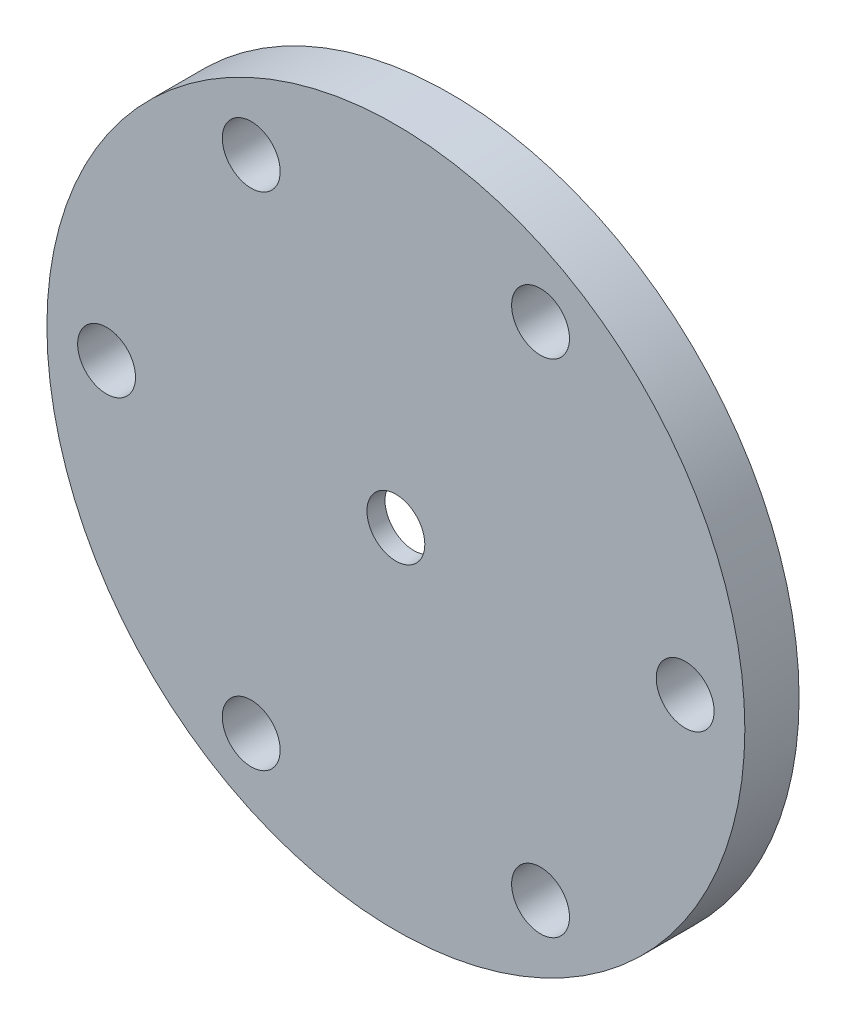
SolidWorks part; units mm, degrees
material "7075-O (SS)"
ref_plane "Front" through (0, 0, 0) normal (0, 0, 1) x (1, 0, 0)
ref_plane "Top" through (0, 0, 0) normal (0, 1, 0) x (1, 0, 0)
ref_plane "Right" through (0, 0, 0) normal (1, 0, 0) x (0, 0, -1)
sketch "Croquis1" plane through (0, 0, 0) normal (0, 0, 1) x (1, 0, 0)
  line L2 (-8, 13.8564) -> (8, -13.8564) construction
  line L3 (0, -55) -> (0, 55) construction
  circle A0 centre (0, 0) radius 19.3
  circle A1 centre (-8, 13.8564) radius 1.6
  circle A2 centre (0, 0) radius 1.6
  circle A3 centre (8, 13.8564) radius 1.6
  circle A4 centre (16, 0) radius 1.6
  circle A5 centre (8, -13.8564) radius 1.6
  circle A6 centre (-8, -13.8564) radius 1.6
  circle A7 centre (-16, 0) radius 1.6
  point P5 (0, 0)
  dimension "D1" = 38.6
  dimension "D2" = 3.2
  dimension "D3" = 32
  dimension "D5" = 30
  dimension "D4" = 6
extrude "Saliente-Extruir1" add sketch "Croquis1" along normal mid plane 3
sketch "Croquis2" plane through (0, 0, -1.5) normal (0, 0, -1) x (-1, 0, 0)
  circle A0 centre (0, 0) radius 12
  circle A1 centre (0, 0) radius 1.6 construction
  circle A2 centre (0, 0) radius 1.6
  dimension "D1" = 24
extrude "Cortar-Extruir1" cut sketch "Croquis2" against normal blind 2
sketch "Croquis4" plane through (0, 0, 1.5) normal (0, 0, 1) x (1, 0, 0)
  line L0 (0, 7.0522) -> (0, 0) construction
  line L1 (0, -55) -> (0, 55) construction
  line L2 (0, 0) -> (-5.2139, 0) construction
  line L3 (55, 0) -> (-55, 0) construction
